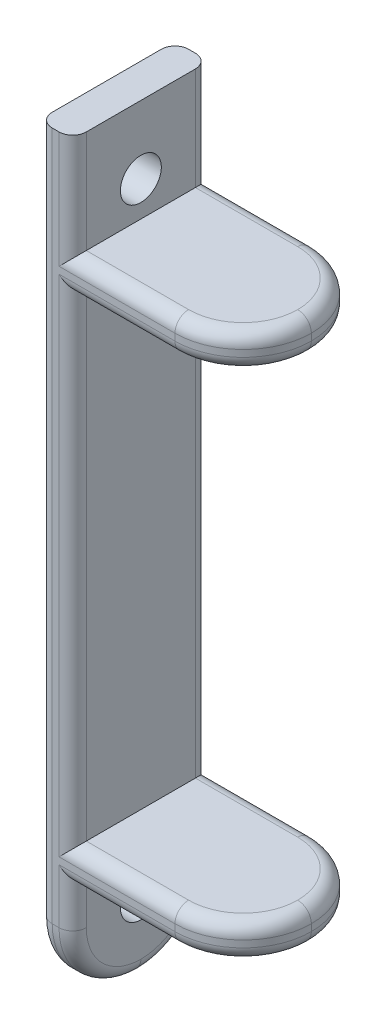
SolidWorks part; units mm, degrees
ref_plane "Front Plane" through (0, 0, 0) normal (0, 0, 1) x (1, 0, 0)
ref_plane "Top Plane" through (0, 0, 0) normal (0, 1, 0) x (1, 0, 0)
ref_plane "Right Plane" through (0, 0, 0) normal (1, 0, 0) x (0, 0, -1)
sketch "Sketch1" plane through (0, 0, 0) normal (0, 0, 1) x (1, 0, 0)
  line L0 (5, 0) -> (5, 10)
  line L1 (0, 0) -> (5, 0)
  line L2 (0, 0) -> (0, 170)
  line L3 (0, 170) -> (5, 170)
  line L4 (5, 0) -> (5, 16)
  line L5 (5, 10) -> (5, 16)
  line L6 (5, 16) -> (30, 16)
  line L7 (5, 21) -> (5, 91)
  line L8 (30, 16) -> (5, 16)
  line L9 (30, 16) -> (30, 21)
  line L10 (30, 21) -> (5, 21)
  line L12 (5, 96) -> (5, 170)
  line L13 (5, 91) -> (30, 91)
  line L15 (5, 96) -> (30, 96)
  line L16 (30, 91) -> (30, 96)
  line L17 (5, 21) -> (5, 91)
  dimension "D1" = 170
  dimension "D2" = 5
  dimension "D3" = 10
  dimension "D4" = 6
  dimension "D5" = 25
  dimension "D6" = 5
  dimension "D7" = 70
  dimension "D8" = 25
  dimension "D9" = 5
extrude "Boss-Extrude1" add sketch "Sketch1" along normal blind 20 contours L13 L16 L15 L12 L3 L2 L1 L0 L4 L6 L9 L10 L7 region at (2.5, 1.7263, 0)
sketch "Sketch2" plane through (0, 0, 0) normal (-1, 0, 0) x (0, 0, 1)
  line L0 (0, 0) -> (0, 170) construction
  line L1 (20, 0) -> (0, 0)
  line L2 (20, 0) -> (20, 20)
  line L3 (20, 20) -> (0, 20)
  line L4 (0, 0) -> (0, 20)
  line L5 (20, 0) -> (20, 170) construction
  line L6 (20, 91.1008) -> (0, 91.1008)
  line L7 (20, 91.1008) -> (20, 111.1008)
  line L8 (20, 111.1008) -> (0, 111.1008)
  line L9 (0, 91.1008) -> (0, 111.1008)
  circle A0 centre (10, 10) radius 3
  circle A1 centre (10, 101.1008) radius 3
  dimension "D3" = 6
  dimension "D4" = 6
  dimension "D1" = 20
  dimension "D2" = 20
extrude "Cut-Extrude1" cut sketch "Sketch2" against normal blind 20 contours A0 | A1
fillet "Fillet1" radius 10 8 edges at (2.5, 170, 20) (2.5, 170, 0) (2.5, 0, 0) (2.5, 0, 20) (30, 18.5, 20) (30, 18.5, 0) (30, 93.5, 0) (30, 93.5, 20)
fillet "Fillet2" radius 2 32 edges at (12.5, 21, 20) (27.0711, 21, 17.0711) (27.0711, 21, 2.9289) (5, 13, 20) (5, 13, 0) (5, 2.9289, 2.9289) (12.5, 16, 0) (27.0711, 16, 2.9289) (27.0711, 16, 17.0711) (12.5, 91, 0) (27.0711, 91, 2.9289) (12.5, 91, 20) (12.5, 96, 0) (27.0711, 96, 2.9289) (27.0711, 96, 17.0711) (5, 128, 0) (5, 167.0711, 2.9289) (5, 167.0711, 17.0711) (0, 2.9289, 17.0711) (0, 2.9289, 2.9289) (0, 85, 0) (0, 167.0711, 2.9289) (0, 167.0711, 17.0711) (12.5, 21, 0) (5, 2.9289, 17.0711) (12.5, 16, 20) (27.0711, 91, 17.0711) (12.5, 96, 20) (5, 128, 20) (0, 85, 20) (5, 56, 20) (5, 56, 0)
sketch "Sketch3" plane through (5, 0, 0) normal (1, 0, 0) x (0, 0, -1)
  line L0 (0, 93) -> (0, 19) construction
  line L9 (0, 91.0643) -> (-20, 91.0643)
  line L10 (0, 91.0643) -> (0, 111.0643)
  line L11 (0, 111.0643) -> (-20, 111.0643)
  line L12 (-20, 91.0643) -> (-20, 111.0643)
  line L13 (-20, 94) -> (-20, 160) construction
  line L15 (5.4118, 111.0643) -> (-29.024, 111.0643)
  line L16 (5.4118, 111.0643) -> (5.4118, 180.5566)
  line L17 (5.4118, 180.5566) -> (-29.024, 180.5566)
  line L18 (-29.024, 111.0643) -> (-29.024, 180.5566)
  line M5 (-2, 96) -> (-2, 160)
  arc M6 (-2, 160) -> (-10, 168) centre (-10, 160) ccw
  arc M7 (-10, 168) -> (-18, 160) centre (-10, 160) ccw
  line M8 (-18, 160) -> (-18, 96)
  dimension "D1" = 20
extrude "Cut-Extrude2" cut sketch "Sketch3" against normal blind 10 contours L18 L15 L11 L16 L17 M8 M7 M6 M5 | L11 M5 M6 M7 M8 region at (5, 111.8399, 1) region at (5, 138.7026, 10)
